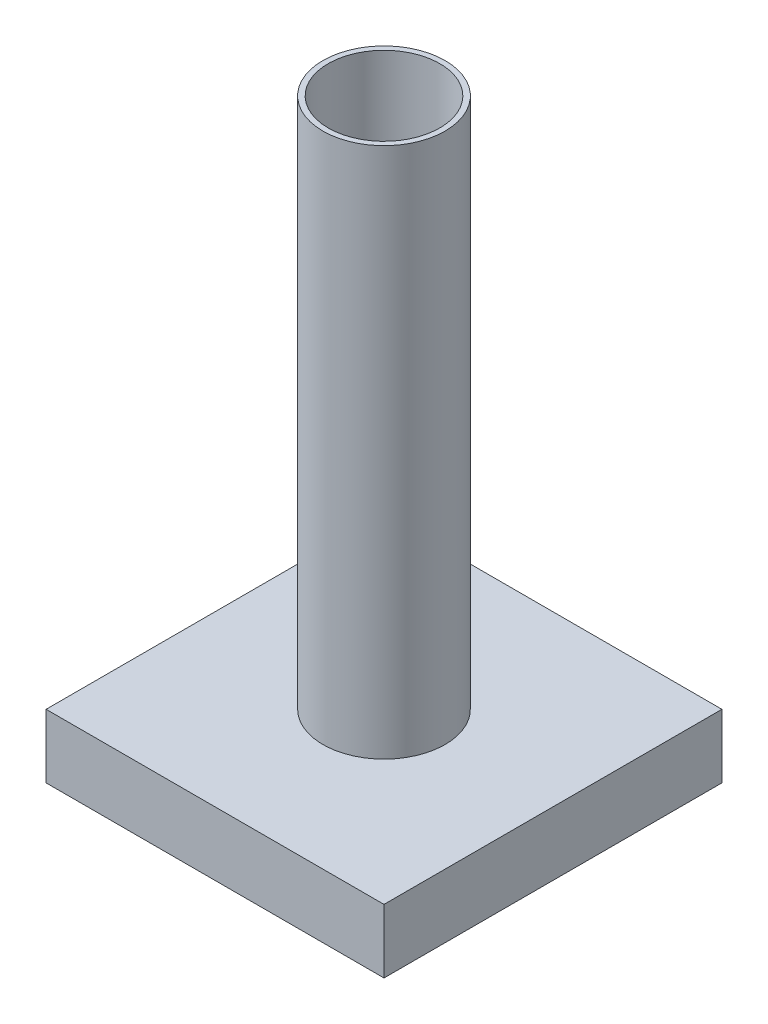
SolidWorks part; units mm, degrees
ref_plane "Front Plane" through (0, 0, 0) normal (0, 0, 1) x (1, 0, 0)
ref_plane "Top Plane" through (0, 0, 0) normal (0, 1, 0) x (1, 0, 0)
ref_plane "Right Plane" through (0, 0, 0) normal (1, 0, 0) x (0, 0, -1)
sketch "Sketch1" plane through (0, 0, 0) normal (0, 1, 0) x (1, 0, 0)
  line L1 (0, 0) -> (31.8, 0)
  line L2 (0, 0) -> (0, 31.8)
  line L3 (0, 31.8) -> (31.8, 31.8)
  line L4 (31.8, 0) -> (31.8, 31.8)
  dimension "D1" = 31.8
  dimension "D2" = 31.8
extrude "Boss-Extrude2" add sketch "Sketch1" against normal blind 6
sketch "Sketch5" plane through (0, -6, 0) normal (0, -1, 0) x (1, 0, 0)
  line L1 (29.8, -2) -> (2, -2)
  line L2 (29.8, -2) -> (29.8, -29.8)
  line L3 (29.8, -29.8) -> (2, -29.8)
  line L4 (2, -2) -> (2, -29.8)
  line L5 (31.8, 0) -> (31.8, -31.8) construction
  line L6 (55, 0) -> (-55, 0) construction
  line L7 (0, -55) -> (0, 55) construction
  line L8 (31.8, -31.8) -> (0, -31.8) construction
  circle A0 centre (23.9, -7.9) radius 2.4
  circle A1 centre (23.9, -7.9) radius 3.255
  circle A2 centre (15.9, -7.9) radius 2.4
  circle A3 centre (15.9, -7.9) radius 3.255
  circle A4 centre (7.9, -7.9) radius 2.4
  circle A5 centre (7.9, -7.9) radius 3.255
  circle A6 centre (15.9, -15.9) radius 2.4
  circle A7 centre (15.9, -15.9) radius 3.255
  circle A8 centre (7.9, -15.9) radius 2.4
  circle A9 centre (7.9, -15.9) radius 3.255
  circle A10 centre (15.9, -23.9) radius 2.4
  circle A11 centre (15.9, -23.9) radius 3.255
  circle A12 centre (7.9, -23.9) radius 2.4
  circle A13 centre (7.9, -23.9) radius 3.255
  circle A14 centre (23.9, -15.9) radius 2.4
  circle A15 centre (23.9, -15.9) radius 3.255
  circle A16 centre (23.9, -23.9) radius 2.4
  circle A17 centre (23.9, -23.9) radius 3.255
  dimension "D5" = 4.8
  dimension "D6" = 6.51
  dimension "D1" = 2
  dimension "D2" = 2
  dimension "D3" = 2
  dimension "D4" = 2
  dimension "D7" = 7.9
  dimension "D8" = 7.9
  dimension "D9" = 3
  dimension "D10" = 3
extrude "Cut-Extrude2" cut sketch "Sketch5" against normal blind 2 contours L1 L4 L3 L2 A17 A15 A13 A11 A9 A7 A5 A3 A1 | A0 | A14 | A16 | A10 | A6 | A2 | A4 | A8 | A12 region at (29.4068, -6, -15.9) region at (23.9, -6, -7.9) region at (15.9, -6, -7.9) region at (7.9, -6, -7.9) region at (15.9, -6, -15.9) region at (7.9, -6, -15.9) region at (15.9, -6, -23.9) region at (7.9, -6, -23.9) region at (23.9, -6, -15.9) region at (23.9, -6, -23.9)
sketch "Sketch6" plane through (0, 0, 0) normal (0, 1, 0) x (1, 0, 0)
  line L0 (31.8, 0) -> (31.8, 31.8) construction
  line L1 (0, 0) -> (31.8, 0) construction
  circle A0 centre (15.9, 15.9) radius 5
  dimension "D1" = 10
  dimension "D2" = 15.9
  dimension "D3" = 15.9
extrude "Cut-Extrude3" cut sketch "Sketch6" against normal blind 2
sketch "Sketch7" plane through (0, 0, 0) normal (0, 1, 0) x (1, 0, 0)
  circle A0 centre (15.9, 15.9) radius 5.25
  circle A1 centre (15.9, 15.9) radius 5.75
  dimension "D1" = 10.5
  dimension "D2" = 11.5
extrude "Boss-Extrude4" add sketch "Sketch7" along normal blind 50
ref_plane "Plane7" through (0, 0, -10.15) normal (0, 0, 1) x (1, 0, 0)
sketch "Sketch9" plane through (0, 0, -10.15) normal (0, 0, 1) x (1, 0, 0)
  line L0 (15.9, 50) -> (15.9, 49)
  line L1 (21.65, 50) -> (10.15, 50) construction
  line L2 (16.9, 50) -> (17.4, 49)
  line L3 (14.9, 48) -> (16.9, 48)
  line L4 (14.9, 48) -> (14.9, 50)
  line L5 (14.9, 50) -> (16.9, 50)
  line L6 (16.9, 48) -> (16.9, 50)
  line L7 (14.9, 48) -> (16.9, 50) construction
  line L8 (14.9, 50) -> (16.9, 48) construction
  line L9 (14.9, 49) -> (14.4, 49)
  line L10 (14.9, 49) -> (14.9, 50)
  line L13 (17.4, 49) -> (16.9, 49)
  line L16 (16.9, 49) -> (16.9, 50)
  line L17 (14.9, 50) -> (14.4, 49)
  dimension "D1" = 1
  dimension "D2" = 2
extrude "Boss-Extrude5" [suppressed] add sketch "Sketch9" along normal blind 1 and the other way blind 0.5 contours L4 L3 L6 L5 | L17 L9 L10 | L2 L13 L16
ref_axis "Axis1" through (15.9, 50, -15.9) along (0, -1, 0)
pattern_circular "CirPattern6" [suppressed] count 4 over 360 about axis through (15.9, 50, -15.9) along (0, -1, 0) of bodies 123 124
